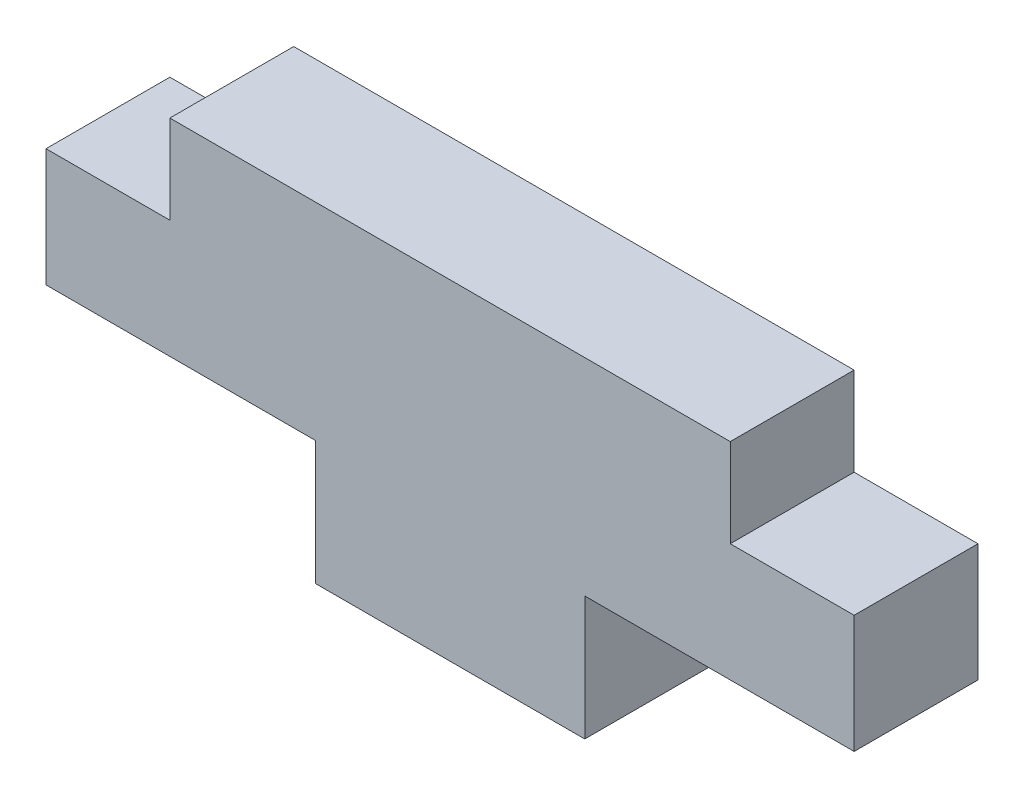
SolidWorks part; units mm, degrees
ref_plane "Front Plane" through (0, 0, 0) normal (0, 0, 1) x (1, 0, 0)
ref_plane "Top Plane" through (0, 0, 0) normal (0, 1, 0) x (1, 0, 0)
ref_plane "Right Plane" through (0, 0, 0) normal (1, 0, 0) x (0, 0, -1)
sketch "Sketch1" plane through (0, 0, 0) normal (0, 0, 1) x (1, 0, 0)
  line L5 (0, 0) -> (24.13, 0)
  line L6 (0, 0) -> (0, 8.89)
  line L7 (0, 8.89) -> (24.13, 8.89)
  line L8 (24.13, 0) -> (24.13, 8.89)
  dimension "D1" = 24.13
  dimension "D2" = 8.89
extrude "Boss-Extrude1" add sketch "Sketch1" along normal blind 5.334 contours L6 L5 L8 L7
sketch "Sketch6" plane through (24.13, 0, 0) normal (1, 0, 0) x (0, 0, -1)
  line L9 (-5.334, 0) -> (-5.334, 8.89) construction
  line L10 (-5.334, 8.89) -> (0, 8.89)
  line L11 (-5.334, 8.89) -> (-5.334, 0)
  line L12 (-5.334, 0) -> (0, 0)
  line L13 (0, 8.89) -> (0, 0)
  line L14 (-5.334, 8.89) -> (0, 8.89) construction
extrude "Boss-Extrude5" add sketch "Sketch6" along normal blind 5.334
sketch "Sketch11" plane through (0, 0, 0) normal (-1, 0, 0) x (0, 0, 1)
  line L1 (0, 10.2062) -> (5.334, 10.2062)
  line L2 (0, 10.2062) -> (0, 0)
  line L3 (0, 0) -> (5.334, 0)
  line L4 (5.334, 10.2062) -> (5.334, 0)
extrude "Boss-Extrude6" add sketch "Sketch11" along normal blind 5.334
sketch "Sketch12" plane through (0, 0, 0) normal (0, -1, 0) x (-1, 0, 0)
  line L1 (-29.464, 0) -> (5.334, 0)
  line L2 (-29.464, 0) -> (-29.464, -5.334)
  line L3 (-29.464, -5.334) -> (5.334, -5.334)
  line L4 (5.334, 0) -> (5.334, -5.334)
extrude "Boss-Extrude7" add sketch "Sketch12" along normal blind 5.334
sketch "Sketch13" plane through (0, 0, 0) normal (0, 0, -1) x (-1, 0, 0)
  line L0 (0, 8.89) -> (5.334, 8.89)
  line L1 (5.334, 10.2062) -> (5.334, -5.334) construction
  line L2 (0, 8.89) -> (0, 10.2062)
  line L3 (5.334, 10.2062) -> (0, 10.2062) construction
  line L4 (0, 10.2062) -> (5.334, 10.2062)
  line L5 (5.334, 10.2062) -> (5.334, 8.89)
extrude "Cut-Extrude1" cut sketch "Sketch13" against normal through all
sketch "Sketch17" plane through (0, -5.334, 0) normal (0, -1, 0) x (-1, 0, 0)
  line L0 (-29.464, -5.334) -> (5.334, -5.334) construction
  line L1 (5.334, 0) -> (-6.2653, 0)
  line L2 (5.334, 0) -> (5.334, -5.334)
  line L3 (5.334, -5.334) -> (-6.2653, -5.334)
  line L4 (-6.2653, 0) -> (-6.2653, -5.334)
  line L5 (-17.8647, 0) -> (-6.2653, 0) construction
  line L6 (-29.464, 0) -> (-17.8647, 0)
  line L7 (-29.464, 0) -> (-29.464, -5.334)
  line L8 (-29.464, -5.334) -> (-17.8647, -5.334)
  line L9 (-17.8647, 0) -> (-17.8647, -5.334)
extrude "Cut-Extrude5" cut sketch "Sketch17" against normal blind 5.334
sketch "Sketch18" plane through (0, 0, 5.334) normal (0, 0, 1) x (1, 0, 0)
  line L0 (17.78, 63.5) -> (17.78, 5.08) construction
  line L1 (-5.334, 8.89) -> (0, 8.89)
  line L2 (-5.334, 8.89) -> (-5.334, 5.08)
  line L3 (-5.334, 5.08) -> (0, 5.08)
  line L4 (0, 8.89) -> (0, 5.08)
  line L5 (17.78, 5.08) -> (29.464, 5.08)
  line L6 (17.78, 5.08) -> (17.78, 8.89)
  line L7 (17.78, 8.89) -> (29.464, 8.89)
  line L8 (29.464, 5.08) -> (29.464, 8.89)
extrude "Cut-Extrude6" cut sketch "Sketch18" against normal blind 5.334
sketch "Sketch19" plane through (17.78, 0, 0) normal (1, 0, 0) x (0, 0, -1)
  line L1 (-5.334, 8.89) -> (0, 8.89)
  line L2 (-5.334, 8.89) -> (-5.334, 5.08)
  line L3 (-5.334, 5.08) -> (0, 5.08)
  line L4 (0, 8.89) -> (0, 5.08)
extrude "Boss-Extrude8" add sketch "Sketch19" along normal blind 5.334
sketch "Sketch20" plane through (23.114, 0, 0) normal (1, 0, 0) x (0, 0, -1)
  line L1 (-5.334, 8.89) -> (0, 8.89)
  line L2 (-5.334, 8.89) -> (-5.334, 5.08)
  line L3 (-5.334, 5.08) -> (0, 5.08)
  line L4 (0, 8.89) -> (0, 5.08)
extrude "Boss-Extrude10" add sketch "Sketch20" along normal blind 1.016
equation "\"Foamcore\" = .1875in"
equation "\"Mdf\"= .21in"
equation "\"Gmaterial\"= \"Mdf\""
equation "\"D1@Boss-Extrude1\"= \"Gmaterial\""
equation "\"D1@Boss-Extrude7\"= \"Gmaterial\""
equation "\"D1@Boss-Extrude6\"= \"Gmaterial\""
equation "\"D1@Boss-Extrude5\"= \"Gmaterial\""
equation "\"D1@Cut-Extrude5\"=\"Gmaterial\""
equation "\"D1@Cut-Extrude6\"=\"Gmaterial\""
equation "\"D1@Boss-Extrude8\"=\"Gmaterial\""
